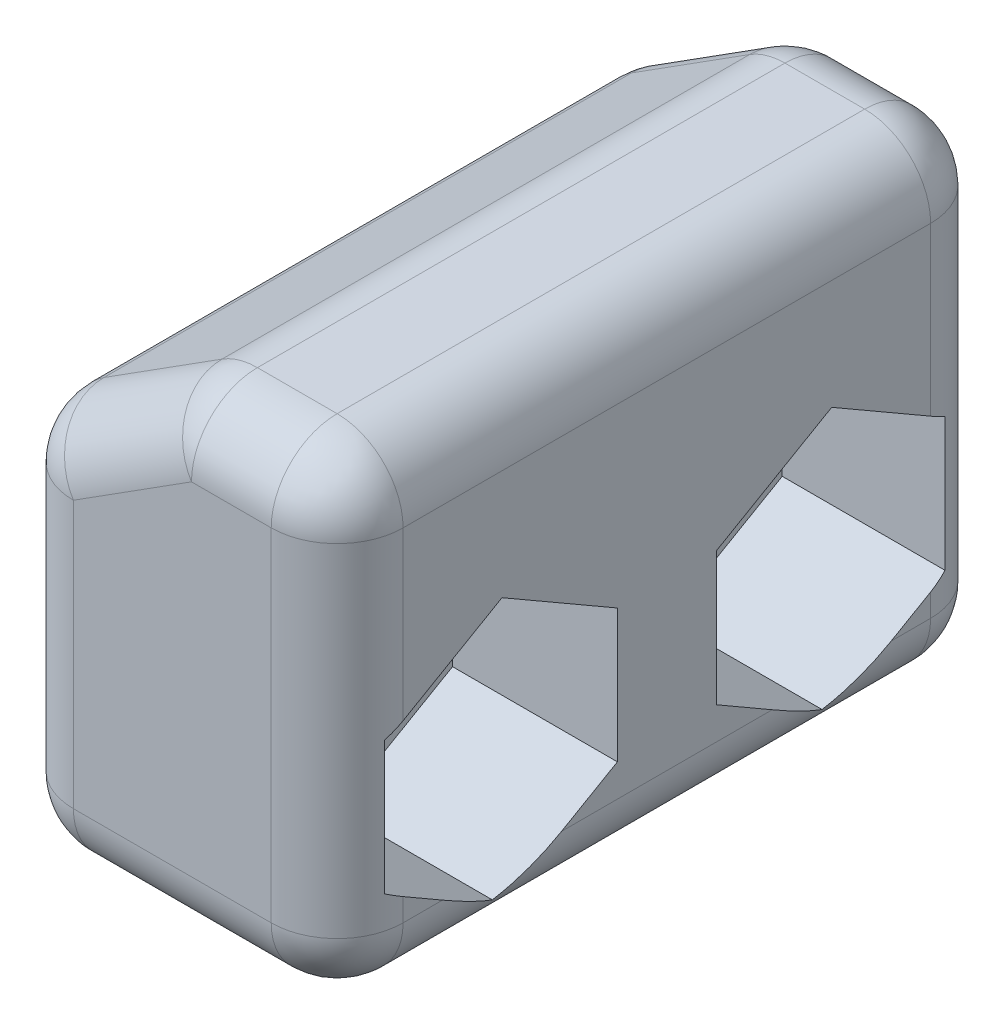
SolidWorks part; units mm, degrees
ref_plane "Front Plane" through (0, 0, 0) normal (0, 0, 1) x (1, 0, 0)
ref_plane "Top Plane" through (0, 0, 0) normal (0, 1, 0) x (1, 0, 0)
ref_plane "Right Plane" through (0, 0, 0) normal (1, 0, 0) x (0, 0, -1)
sketch "Sketch3" plane through (0, 0, 0) normal (0, 0, 1) x (1, 0, 0)
  line L0 (0, 14.224) -> (6.35, 18.2562)
  line L1 (6.35, 18.2562) -> (12.7, 18.2563)
  line L2 (12.7, 18.2563) -> (12.7, 0)
  line L3 (12.7, 0) -> (0, 0)
  line L4 (0, 0) -> (0, 14.224)
  point P3 (0, 0)
  point P7 (0, 14.0162)
  dimension "D1" = 18.2562
  dimension "D2" = 6.35
  dimension "D3" = 6.35
  dimension "D4" = 14.224
extrude "Boss-Extrude1" add sketch "Sketch3" along normal blind 25.4
sketch "Sketch4" plane through (0, 0, 0) normal (-1, 0, 0) x (0, 0, 1)
  line L0 (25.4, 0) -> (0, 0) construction
  line L1 (6.35, 6.35) -> (0, 6.35) construction
  line L2 (0, 14.224) -> (0, 0) construction
  line L3 (19.05, 6.35) -> (25.4, 6.35) construction
  line L4 (25.4, 14.224) -> (25.4, 0) construction
  circle A0 centre (6.35, 6.35) radius 2.159
  circle A1 centre (19.05, 6.35) radius 2.159
  point P9 (0, 0)
  dimension "D1" = 6.35
  dimension "D2" = 12.7
  dimension "D3" = 4.318
extrude "Cut-Extrude1" cut sketch "Sketch4" against normal through all
sketch "Sketch6" plane through (12.7, 0, 0) normal (1, 0, 0) x (0, 0, -1)
  line L0 (-25.4, 0) -> (-25.4, 18.2562) construction
  line L1 (-14.605, 8.9163) -> (-19.05, 11.4826)
  line L2 (-19.05, 11.4826) -> (-23.495, 8.9163)
  line L3 (-23.495, 8.9163) -> (-23.495, 3.7837)
  line L4 (-23.495, 3.7837) -> (-19.05, 1.2174)
  line L5 (-19.05, 1.2174) -> (-14.605, 3.7837)
  line L6 (-14.605, 3.7837) -> (-14.605, 8.9163)
  line L8 (-1.905, 3.7837) -> (-1.905, 8.9163)
  line L9 (-1.905, 8.9163) -> (-6.35, 11.4826)
  line L10 (-6.35, 11.4826) -> (-10.795, 8.9163)
  line L11 (-10.795, 8.9163) -> (-10.795, 3.7837)
  line L12 (-10.795, 3.7837) -> (-6.35, 1.2174)
  line L13 (-6.35, 1.2174) -> (-1.905, 3.7837)
  circle A0 centre (-19.05, 6.35) radius 4.445 construction
  circle A1 centre (-6.35, 6.35) radius 4.445 construction
  dimension "D1" = 8.89
  dimension "D2" = 8.89
extrude "Cut-Extrude2" cut sketch "Sketch6" against normal blind 6.35
fillet "Fillet1" radius 2.54 15 edges at (0, 0, 12.7) (12.7, 0, 12.7) (12.7, 18.2563, 12.7) (6.35, 18.2562, 12.7) (3.175, 16.2401, 25.4) (9.525, 18.2563, 25.4) (12.7, 9.1281, 25.4) (6.35, 0, 25.4) (0, 7.112, 25.4) (6.35, 0, 0) (12.7, 9.1281, 0) (9.525, 18.2563, 0) (3.175, 16.2401, 0) (0, 7.112, 0) (0, 14.224, 12.7)
